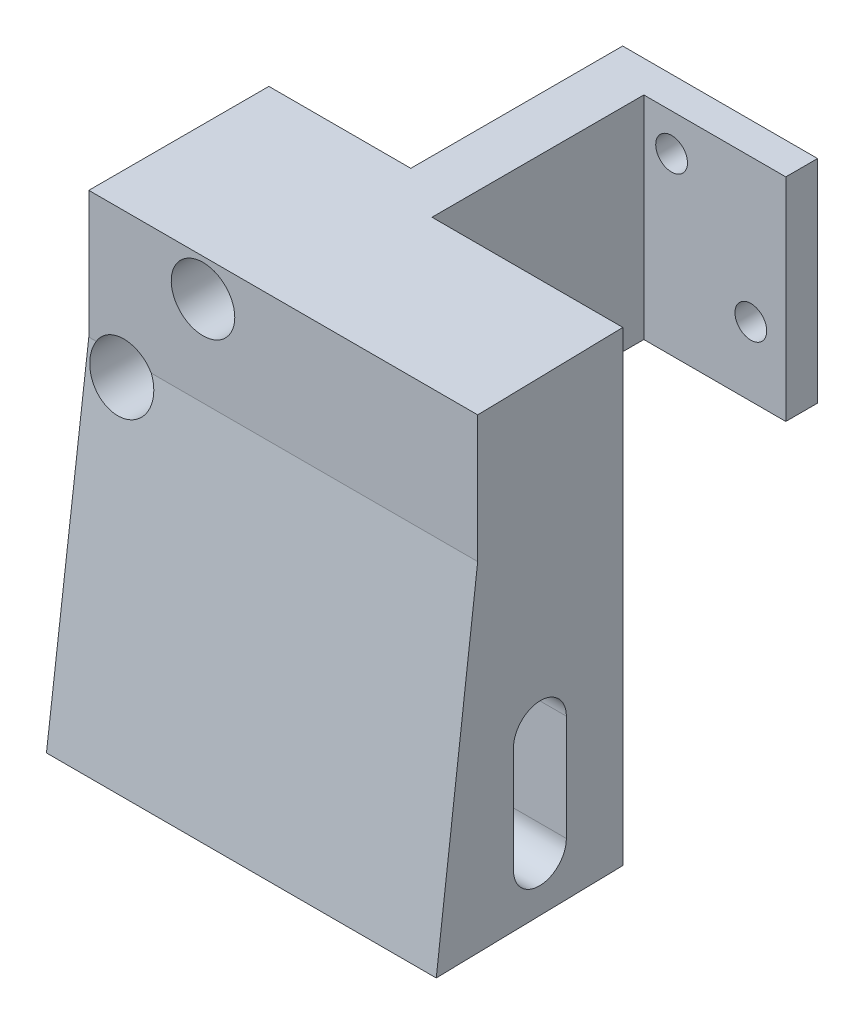
SolidWorks part; units mm, degrees
ref_plane "Front Plane" through (0, 0, 0) normal (0, 0, 1) x (1, 0, 0)
ref_plane "Top Plane" through (0, 0, 0) normal (0, 1, 0) x (1, 0, 0)
ref_plane "Right Plane" through (0, 0, 0) normal (1, 0, 0) x (0, 0, -1)
sketch "Sketch1" plane through (0, 0, 0) normal (0, 1, 0) x (1, 0, 0)
  line L0 (0, 0) -> (18.4, 0)
  line L1 (18.4, 0) -> (18.4, 20)
  line L2 (18.4, 20) -> (31.8, 20)
  line L3 (31.8, 20) -> (31.8, 23)
  line L4 (31.8, 23) -> (13.4, 23)
  line L5 (13.4, 23) -> (13.4, 3)
  line L6 (13.4, 3) -> (0, 3)
  line L7 (0, 3) -> (0, 0)
  dimension "D1" = 13.4
  dimension "D2" = 5
  dimension "D3" = 3
  dimension "D4" = 17
extrude "Boss-Extrude1" add sketch "Sketch1" along normal blind 20
sketch "Sketch2" plane through (0, 0, -20) normal (0, 0, 1) x (1, 0, 0)
  line L1 (31.8, 20) -> (31.8, 0) construction
  line L2 (31.8, 0) -> (13.4, 0) construction
  circle A0 centre (28.5, 6.5) radius 1.5
  circle A1 centre (21.02, 16.5) radius 1.5
  dimension "D1" = 3
  dimension "D2" = 6.5
  dimension "D3" = 3.3
  dimension "D4" = 10.78
  dimension "D5" = 16.5
extrude "Cut-Extrude1" cut sketch "Sketch2" against normal through all both and the other way through all
ref_plane "Plane1" through (15.9, 0, 0) normal (-1, 0, 0) x (0, 0, 1)
mirror "Mirror1" about plane through (15.9, 0, 0) normal (-1, 0, 0) of "Cut-Extrude1"
sketch "Sketch3" plane through (0, 0, 0) normal (-1, 0, 0) x (0, 0, 1)
  line L0 (0, 0) -> (0, -24)
  line L1 (0, -24) -> (18, -24)
  line L2 (18, -24) -> (14, 8)
  line L3 (14, 8) -> (14, 20)
  line L4 (14, 20) -> (0, 20)
  line L5 (0, 20) -> (0, 0) construction
  line L6 (0, 20) -> (0, 0)
  line L7 (8, -9) -> (8, -19) construction
  line L8 (10.55, -9) -> (10.55, -19)
  line L9 (5.45, -9) -> (5.45, -19)
  arc A0 (10.55, -9) -> (5.45, -9) centre (8, -9) ccw
  arc A1 (5.45, -19) -> (10.55, -19) centre (8, -19) ccw
  point P3 (8, -14)
  dimension "D1" = 18
  dimension "D2" = 14
  dimension "D3" = 12
  dimension "D4" = 44
  dimension "D5" = 10
  dimension "D6" = 5.1
  dimension "D7" = 8
  dimension "D8" = 5
extrude "Boss-Extrude2" add sketch "Sketch3" against normal offset from surface (36.8 mm away) 5 up to face at (31.8, 10, -21.5) offset beyond the face yes
sketch "Sketch4" plane through (0, -24, 0) normal (0, -1, 0) x (1, 0, 0)
  line L4 (36.8, 18) -> (36.4167, 0)
  line L5 (36.8, 0) -> (0, 0) construction
  line L6 (36.4167, 0) -> (36.8, 0)
  line L7 (36.8, 0) -> (36.8, 18)
  dimension "D1" = 1.22
extrude "Cut-Extrude2" cut sketch "Sketch4" against normal through all
sketch "Sketch5" plane through (0, 0, 0) normal (-1, 0, 0) x (0, 0, 1)
  line L0 (14, -9) -> (14, -24)
  line L1 (0, -24) -> (18, -24) construction
  line L2 (14, -24) -> (2, -24)
  line L3 (2, -24) -> (2, -9)
  arc A0 (14, -9) -> (2, -9) centre (8, -9) ccw
  arc A1 (10.55, -9) -> (5.45, -9) centre (8, -9) ccw construction
  point P10 (0, 0)
  dimension "D1" = 12
extrude "Cut-Extrude3" cut sketch "Sketch5" against normal offset from surface (31.7137 mm away) 5 up to face at (36.6126, 0, 9.2)
sketch "Sketch6" plane through (0, 0, 0) normal (0, 0, -1) x (-1, 0, 0)
  circle A0 centre (-3.3, 6.5) radius 3
  circle A1 centre (-10.78, 16.5) radius 3
  dimension "D1" = 6
extrude "Cut-Extrude4" cut sketch "Sketch6" against normal through all
